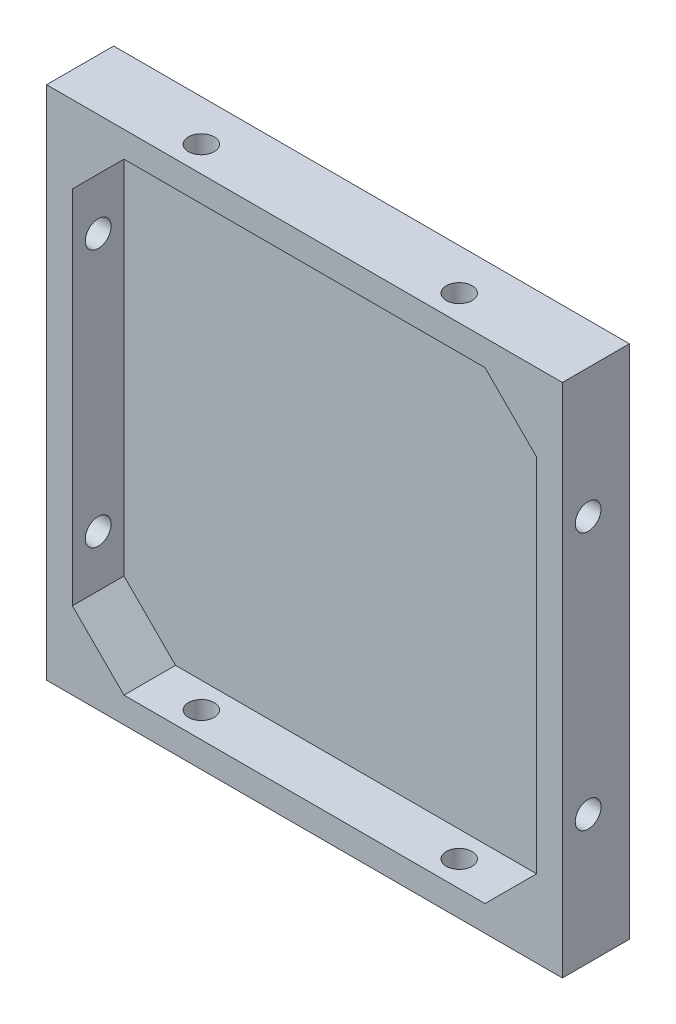
SolidWorks part; units mm, degrees
ref_plane "Plan de face" through (0, 0, 0) normal (0, 0, 1) x (1, 0, 0)
ref_plane "Plan de dessus" through (0, 0, 0) normal (0, 1, 0) x (1, 0, 0)
ref_plane "Plan de droite" through (0, 0, 0) normal (1, 0, 0) x (0, 0, -1)
sketch "Esquisse1" plane through (0, 0, 0) normal (0, 0, 1) x (1, 0, 0)
  line L0 (44.1184, 33.7284) -> (54.1184, 33.7284)
  line L1 (-45.8816, 33.7284) -> (44.1184, 33.7284)
  line L2 (-45.8816, 33.7284) -> (-45.8816, -66.2716)
  line L3 (-45.8816, -66.2716) -> (54.1184, -66.2716)
  line L4 (54.1184, 23.7284) -> (54.1184, -66.2716)
  line L5 (54.1184, 33.7284) -> (54.1184, 23.7284)
  point P6 (54.1184, 33.7284)
  dimension "D1" = 100
  dimension "D2" = 100
extrude "Boss.-Extru.1" add sketch "Esquisse1" along normal blind 13
shell "Coque1" thickness 5 removed face at (4.1184, -16.2716, 13)
sketch "Esquisse2" plane through (-45.8816, 0, 0) normal (-1, 0, 0) x (0, 0, 1)
  line L0 (13, 33.7284) -> (13, -66.2716) construction
  line L1 (13, 33.7284) -> (0, 33.7284) construction
  line L2 (13, -66.2716) -> (0, -66.2716) construction
  circle A0 centre (8, 8.7284) radius 2.5
  circle A1 centre (8, -41.2716) radius 2.5
  dimension "D1" = 5
  dimension "D2" = 5
  dimension "D3" = 5
  dimension "D4" = 5
  dimension "D5" = 25
  dimension "D6" = 25
extrude "Enlèv. mat.-Extru.1" cut sketch "Esquisse2" against normal up to surface (100 mm away) contours A1 | A0 region at (-45.8816, -41.2716, 8) up to face at (54.1184, -16.2716, 6.5)
sketch "Esquisse3" plane through (0, -66.2716, 0) normal (0, -1, 0) x (1, 0, 0)
  line L0 (-45.8816, 13) -> (54.1184, 13) construction
  line L2 (54.1184, 13) -> (54.1184, 0) construction
  line L3 (-45.8816, 13) -> (-45.8816, 0) construction
  circle A0 centre (-20.8816, 8) radius 2.5
  circle A1 centre (29.1184, 8) radius 2.5
  dimension "D1" = 5
  dimension "D2" = 5
  dimension "D3" = 5
  dimension "D4" = 5
  dimension "D5" = 25
  dimension "D6" = 25
extrude "Enlèv. mat.-Extru.2" cut sketch "Esquisse3" against normal up to surface (100 mm away) up to face at (4.1184, 33.7284, 6.5)
sketch "Esquisse4" plane through (0, 0, 3) normal (0, 0, 1) x (1, 0, 0)
  line L0 (-30.8816, 28.7284) -> (-40.8816, 18.7284)
  line L1 (49.1184, 28.7284) -> (-40.8816, 28.7284) construction
  line L2 (-40.8816, 28.7284) -> (-40.8816, -61.2716) construction
  line L3 (-40.8816, 18.7284) -> (-40.8816, 28.7284)
  line L4 (-40.8816, 28.7284) -> (-30.8816, 28.7284)
  line L5 (49.1184, 28.7284) -> (49.1184, 18.7284)
  line L6 (49.1184, -61.2716) -> (49.1184, 28.7284) construction
  line L7 (49.1184, 18.7284) -> (39.1184, 28.7284)
  line L8 (39.1184, 28.7284) -> (49.1184, 28.7284)
  line L9 (49.1184, 28.7284) -> (-40.8816, 28.7284) construction
  line L10 (49.1184, -61.2716) -> (49.1184, -51.2716)
  line L11 (49.1184, -51.2716) -> (39.1184, -61.2716)
  line L12 (-40.8816, -61.2716) -> (49.1184, -61.2716) construction
  line L13 (39.1184, -61.2716) -> (49.1184, -61.2716)
  line L14 (-30.8816, -61.2716) -> (-40.8816, -51.2716)
  line L15 (-40.8816, 28.7284) -> (-40.8816, -61.2716) construction
  line L16 (-40.8816, -51.2716) -> (-40.8816, -61.2716)
  line L17 (-40.8816, -61.2716) -> (-30.8816, -61.2716)
  dimension "D1" = 10
  dimension "D2" = 10
  dimension "D3" = 10
  dimension "D4" = 10
  dimension "D5" = 10
  dimension "D6" = 10
  dimension "D7" = 10
  dimension "D8" = 10
extrude "Boss.-Extru.2" add sketch "Esquisse4" along normal up to surface (10 mm away) up to face at (4.1184, -16.2716, 13)
